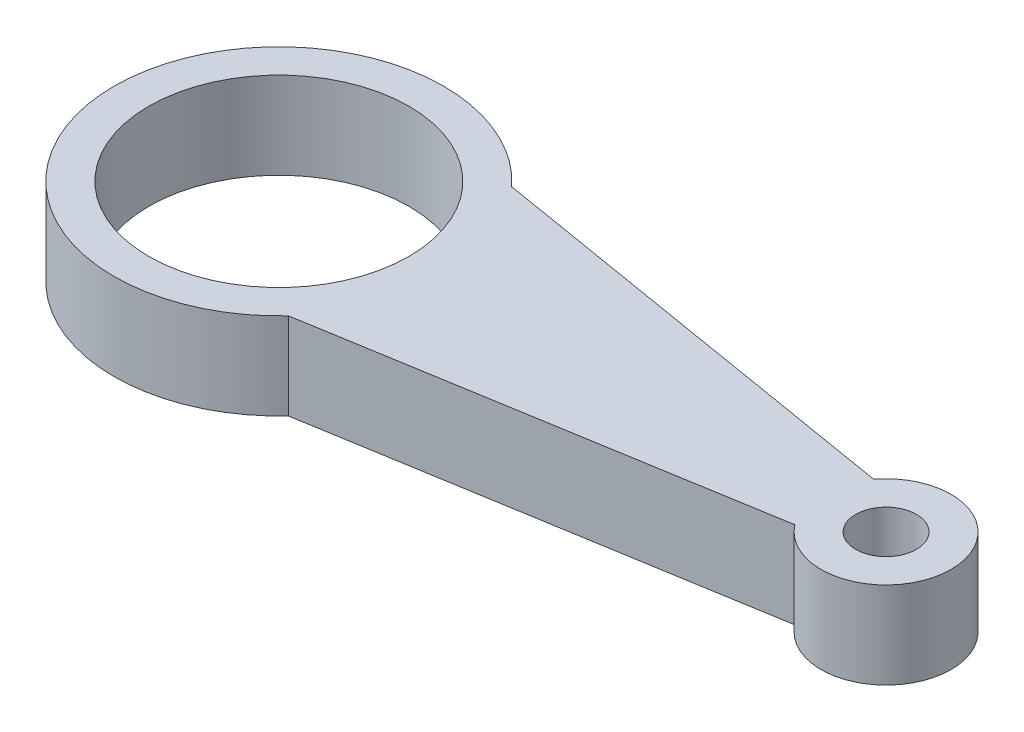
SolidWorks part; units mm, degrees
ref_plane "Front Plane" through (0, 0, 0) normal (0, 0, 1) x (1, 0, 0)
ref_plane "Top Plane" through (0, 0, 0) normal (0, 1, 0) x (1, 0, 0)
ref_plane "Right Plane" through (0, 0, 0) normal (1, 0, 0) x (0, 0, -1)
sketch "Sketch1" plane through (0, 0, 0) normal (0, 1, 0) x (1, 0, 0)
  line L0 (-49.1456, 0) -> (183.8958, 0) construction
  line L1 (27.9355, 25.7606) -> (128.0638, 9.0844)
  line L2 (27.9355, -25.7606) -> (128.0638, -9.0844)
  circle A0 centre (0, 0) radius 30
  arc A1 (27.9355, 25.7606) -> (27.9355, -25.7606) centre (0, 0) ccw
  circle A2 centre (140, 0) radius 7
  arc A3 (128.0638, -9.0844) -> (128.0638, 9.0844) centre (140, 0) ccw
  dimension "D1" = 60
  dimension "D2" = 76
  dimension "D3" = 14
  dimension "D4" = 30
  dimension "D5" = 140
extrude "Boss-Extrude1" add sketch "Sketch1" along normal mid plane 20
sketch "Sketch2" plane through (0, 10, 0) normal (0, 1, 0) x (1, 0, 0)
  line L1 (44.6331, 17.4039) -> (107.4288, 6.9454)
  line L2 (128.0638, 9.0844) -> (27.9355, 25.7606) construction
  line L3 (133, 0) -> (30, 0) construction
  arc A7 (36.9092, -9.0395) -> (35.8069, 12.7226) centre (0, 0) ccw
  point P4 (36.9092, 8.5589)
  point P5 (44.6331, 17.4039)
  point P6 (44.6331, 17.4039)
  point P7 (35.8069, 12.7226)
  dimension "D1" = 5.5
